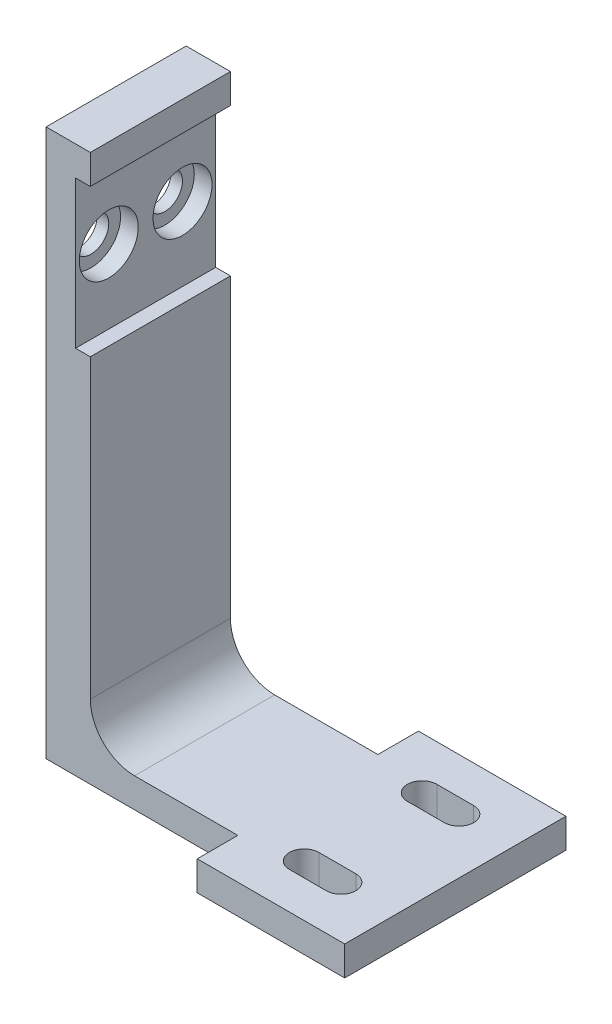
SolidWorks part; units mm, degrees
material "6061-T6 (SS)"
ref_plane "Front Plane" through (0, 0, 0) normal (0, 0, 1) x (1, 0, 0)
ref_plane "Top Plane" through (0, 0, 0) normal (0, 1, 0) x (1, 0, 0)
ref_plane "Right Plane" through (0, 0, 0) normal (1, 0, 0) x (0, 0, -1)
sketch "Sketch1" plane through (0, 0, 0) normal (0, 0, 1) x (1, 0, 0)
  line L0 (-15.4886, 22) -> (-17.5374, 22) construction
  line L9 (-17.5374, 17) -> (-17.5374, 27)
  line L10 (-19.5374, 0) -> (-19.5374, 29)
  line L11 (-19.5374, 29) -> (-16.5374, 29)
  line L12 (-16.5374, 29) -> (-16.5374, 27)
  line L17 (-12.4274, -6.11) -> (3.4626, -6.11)
  line L18 (3.4626, -6.11) -> (3.4626, -8.11)
  line L19 (3.4626, -8.11) -> (-11.4274, -8.11)
  line L20 (-17.5374, 27) -> (-16.5374, 27)
  line L21 (-17.5374, 17) -> (-16.5374, 17)
  line L22 (-16.5374, 17) -> (-16.5374, 14)
  line L23 (-19.5374, 0) -> (-19.5374, -8.11)
  line L24 (-19.5374, -8.11) -> (-11.4274, -8.11)
  line L25 (-16.5374, 14) -> (-16.5374, -6.11)
  line L26 (-16.5374, -6.11) -> (-12.4274, -6.11)
  line L29 (-12.4274, -6.11) -> (-10.0144, -6.11) construction
  point P15 (-17.5374, 22)
  point P21 (-12.4274, 0)
  dimension "D3" = 37.11
  dimension "D4" = 3
  dimension "D2" = 3
  dimension "D5" = 23
  dimension "D6" = 10
  dimension "D7" = 2
  dimension "D8" = 1
  dimension "D10" = 2
extrude "Boss-Extrude1" add sketch "Sketch1" along normal mid plane 9.5
sketch "Sketch2" plane through (-17.5374, 0, 0) normal (1, 0, 0) x (0, 0, -1)
  line L0 (-4.75, 22) -> (4.75, 22) construction
  line L1 (-4.75, 17) -> (-4.75, 27) construction
  line L2 (4.75, 17) -> (4.75, 27) construction
  point P6 (0, 0)
  point P8 (-2.5, 22)
  point P9 (0, 22)
  point P11 (2.5, 22)
  dimension "D2" = 2.5
  dimension "D1" = 2.5
hole_wizard "M2 Clearance Hole1" positions "3DSketch1" profile "Sketch3" hole size "M2" standard "ANSI Metric" end condition through all
sketch3d "3DSketch1"
  point P0 (-17.5374, 22, 2.5)
  point P3 (-17.5374, 22, -2.5)
sketch "Sketch3" plane through (-17.5374, 22, 2.5) normal (0, 1, 0) x (0, 0, -1)
  line L0 (0, 0) -> (0, 2)
  line L1 (0, 2) -> (1.2, 2)
  line L2 (1.2, 2) -> (1.2, 0)
  line L5 (1.2, 0) -> (0, 0)
  line L11 (0, -6.35) -> (0, 107.95) construction
  dimension "Thru Hole Dia." = 2.4
  dimension "Thru Hole Depth" = 2
sketch "Sketch4" plane through (-17.5374, 0, 0) normal (1, 0, 0) x (0, 0, -1)
  circle A0 centre (-2.5, 22) radius 2
  circle A1 centre (2.5, 22) radius 2
  dimension "D1" = 4
  dimension "D2" = 4
extrude "Cut-Extrude1" cut sketch "Sketch4" against normal blind 1.2
sketch "Sketch5" plane through (0, -8.11, 0) normal (0, -1, 0) x (1, 0, 0)
  line L0 (3.4626, -7.5) -> (3.4626, 7.5)
  line L1 (3.4626, 4.75) -> (3.4626, -4.75) construction
  line L2 (3.4626, 7.5) -> (-6.5374, 7.5)
  line L3 (-6.5374, 7.5) -> (-6.5374, -7.5)
  line L4 (-6.5374, -7.5) -> (3.4626, -7.5)
  point P3 (3.4626, 0)
  dimension "D1" = 10
  dimension "D2" = 15
extrude "Boss-Extrude2" add sketch "Sketch5" against normal blind 2
sketch "Sketch6" plane through (0, -6.11, 0) normal (0, 1, 0) x (1, 0, 0)
  line L0 (3.4626, 0) -> (-6.5374, 0) construction
  line L1 (3.4626, 7.5) -> (3.4626, -7.5) construction
  line L2 (-0.2874, -4) -> (-2.7874, -4) construction
  line L3 (-1.5374, -7.5) -> (-1.5374, 7.5) construction
  line L4 (3.4626, -7.5) -> (-6.5374, -7.5) construction
  line L5 (-6.5374, 7.5) -> (3.4626, 7.5) construction
  line L6 (-0.2874, -5) -> (-2.7874, -5)
  line L7 (-0.2874, -3) -> (-2.7874, -3)
  line L8 (-0.2874, 4) -> (-2.7874, 4) construction
  line L9 (-0.2874, 5) -> (-2.7874, 5)
  line L10 (-0.2874, 3) -> (-2.7874, 3)
  arc A0 (-0.2874, -5) -> (-0.2874, -3) centre (-0.2874, -4) ccw
  arc A1 (-2.7874, -3) -> (-2.7874, -5) centre (-2.7874, -4) ccw
  arc A2 (-0.2874, 5) -> (-0.2874, 3) centre (-0.2874, 4) cw
  arc A3 (-2.7874, 3) -> (-2.7874, 5) centre (-2.7874, 4) cw
  point P12 (-1.5374, -4)
  point P13 (-1.5374, 0)
  point P14 (-1.5374, 4)
  point P15 (-1.5374, -4)
  point P23 (-1.5374, 4)
  dimension "D3" = 1
  dimension "D1" = 4
  dimension "D2" = 2.5
extrude "Cut-Extrude2" cut sketch "Sketch6" against normal up to surface (2 mm away) up to face at (-7.2874, -8.11, 0)
fillet "Fillet1" radius 3 1 edges at (-16.5374, -6.11, 0)
